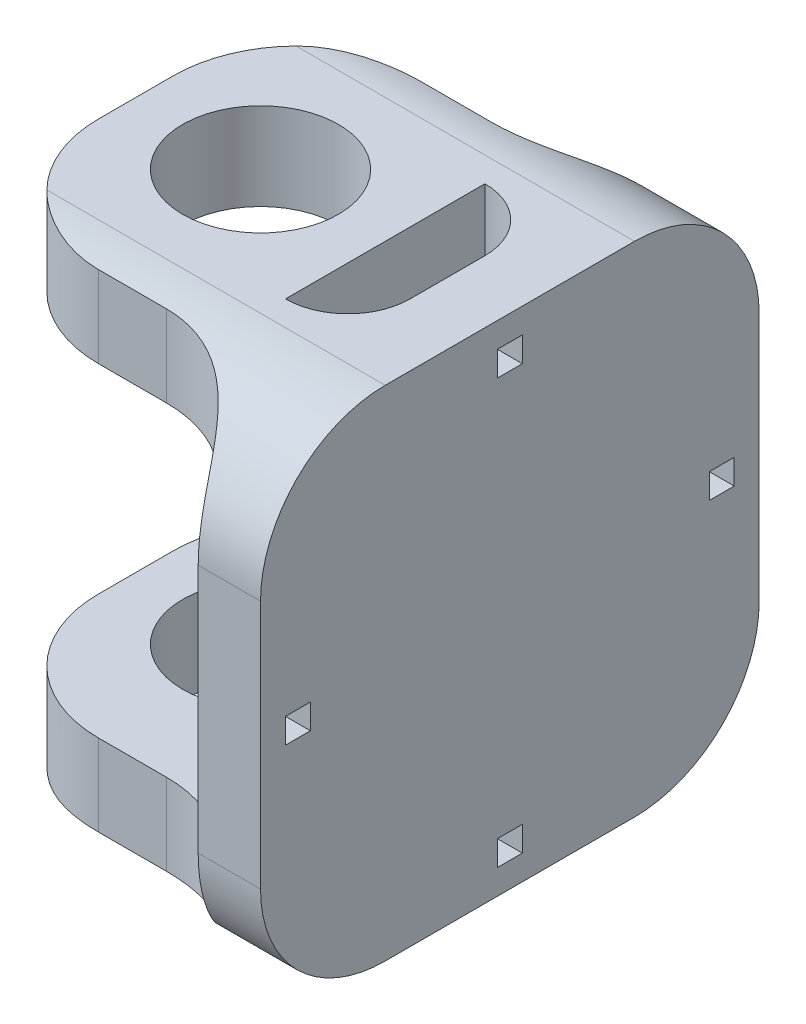
SolidWorks part; units mm, degrees
ref_plane "前视基准面" through (0, 0, 0) normal (0, 0, 1) x (1, 0, 0)
ref_plane "上视基准面" through (0, 0, 0) normal (0, 1, 0) x (1, 0, 0)
ref_plane "右视基准面" through (0, 0, 0) normal (1, 0, 0) x (0, 0, -1)
other "Configuration Table"
sketch "草图1" plane through (0, 0, 0) normal (1, 0, 0) x (0, 0, -1)
  line L1 (-20, -20) -> (20, -20)
  line L2 (-20, -20) -> (-20, 20)
  line L3 (-20, 20) -> (20, 20)
  line L4 (20, -20) -> (20, 20)
  line L5 (-20, -20) -> (20, 20) construction
  line L6 (-20, 20) -> (20, -20) construction
  point P0 (0, 0)
  dimension "D1" = 40
  dimension "D2" = 40
extrude "凸台-拉伸1" add sketch "草图1" along normal blind 5
sketch "草图2" plane through (0, 0, 0) normal (-1, 0, 0) x (0, 0, 1)
  line L0 (-20, 0) -> (20, 0) construction
  line L1 (-20, -20) -> (-20, 20) construction
  line L2 (20, 20) -> (20, -20) construction
  line L3 (0, 20) -> (0, -20) construction
  line L4 (-20, 20) -> (20, 20) construction
  line L5 (20, -20) -> (-20, -20) construction
  line L7 (-18, 1) -> (-16, 1)
  line L8 (-18, 1) -> (-18, -1)
  line L9 (-18, -1) -> (-16, -1)
  line L10 (-16, 1) -> (-16, -1)
  line L11 (16, 1) -> (18, 1)
  line L12 (16, 1) -> (16, -1)
  line L13 (16, -1) -> (18, -1)
  line L14 (18, 1) -> (18, -1)
  line L15 (-1, 18) -> (1, 18)
  line L16 (-1, 18) -> (-1, 16)
  line L17 (-1, 16) -> (1, 16)
  line L18 (1, 18) -> (1, 16)
  line L19 (-1, -16) -> (1, -16)
  line L20 (-1, -16) -> (-1, -18)
  line L21 (-1, -18) -> (1, -18)
  line L22 (1, -16) -> (1, -18)
  dimension "D1" = 2
  dimension "D2" = 1
  dimension "D3" = 2
  dimension "D4" = 1
  dimension "D5" = 2
  dimension "D6" = 1
  dimension "D7" = 2
  dimension "D8" = 1
  dimension "D9" = 2
  dimension "D10" = 2
  dimension "D11" = 2
  dimension "D12" = 2
  dimension "D13" = 2
  dimension "D14" = 2
  dimension "D15" = 2
  dimension "D16" = 2
extrude "切除-拉伸1" cut sketch "草图2" against normal blind 5
sketch "草图3" plane through (0, 0, 0) normal (-1, 0, 0) x (0, 0, 1)
  line L0 (0, 20) -> (0, -20) construction
  line L1 (-20, 20) -> (20, 20) construction
  line L2 (20, -20) -> (-20, -20) construction
  line L3 (-20, 0) -> (20, 0) construction
  line L4 (-20, -20) -> (-20, 20) construction
  line L5 (20, 20) -> (20, -20) construction
  line L7 (-13, 20) -> (-8, 20)
  line L8 (-13, 20) -> (-13, 13)
  line L9 (-13, 13) -> (-8, 13)
  line L10 (-8, 20) -> (-8, 13)
  line L11 (8, 20) -> (13, 20)
  line L12 (8, 20) -> (8, 13)
  line L13 (8, 13) -> (13, 13)
  line L14 (13, 20) -> (13, 13)
  dimension "D1" = 8
  dimension "D2" = 8
  dimension "D3" = 5
  dimension "D4" = 5
  dimension "D5" = 7
  dimension "D6" = 7
extrude "凸台-拉伸2" add sketch "草图3" along normal blind 25
sketch "草图4" plane through (0, 0, 8) normal (0, 0, -1) x (-1, 0, 0)
  line L0 (25, 13) -> (0, 13) construction
  line L1 (25, 20) -> (5, 20)
  line L2 (25, 20) -> (25, 13)
  line L3 (25, 13) -> (5, 13)
  line L4 (5, 20) -> (5, 13)
  dimension "D1" = 20
extrude "凸台-拉伸3" add sketch "草图4" along normal up to next
sketch "草图5" plane through (0, 20, 0) normal (0, 1, 0) x (1, 0, 0)
  line L0 (-25, 0) -> (-5, 0) construction
  line L1 (-25, -13) -> (-25, 13) construction
  line L2 (-5, 8) -> (-5, -8) construction
  circle A0 centre (-15, 0) radius 6.25
  dimension "D1" = 12.5
extrude "切除-拉伸2" cut sketch "草图5" against normal blind 10
fillet "圆角1" radius 10 2 edges at (-25, 16.5, -13) (-25, 16.5, 13)
fillet "圆角2" radius 10 2 edges at (0, 16.5, -13) (0, 16.5, 13)
fillet "圆角3" radius 5 2 edges at (0, 16.5, 8) (0, 16.5, -8)
fillet "圆角4" radius 5 2 edges at (0, 13, -11.5) (0, 13, 11.5)
ref_plane "基准面1" through (0, 0, 0) normal (0, 1, 0) x (1, 0, 0)
mirror "镜向1" about plane through (0, 0, 0) normal (0, 1, 0) of "凸台-拉伸2", "凸台-拉伸3", "切除-拉伸2", "圆角2", "圆角1", "圆角3", "圆角4"
fillet "圆角5" radius 10 4 edges at (2.5, -20, 20) (2.5, -20, -20) (2.5, 20, -20) (2.5, 20, 20)
